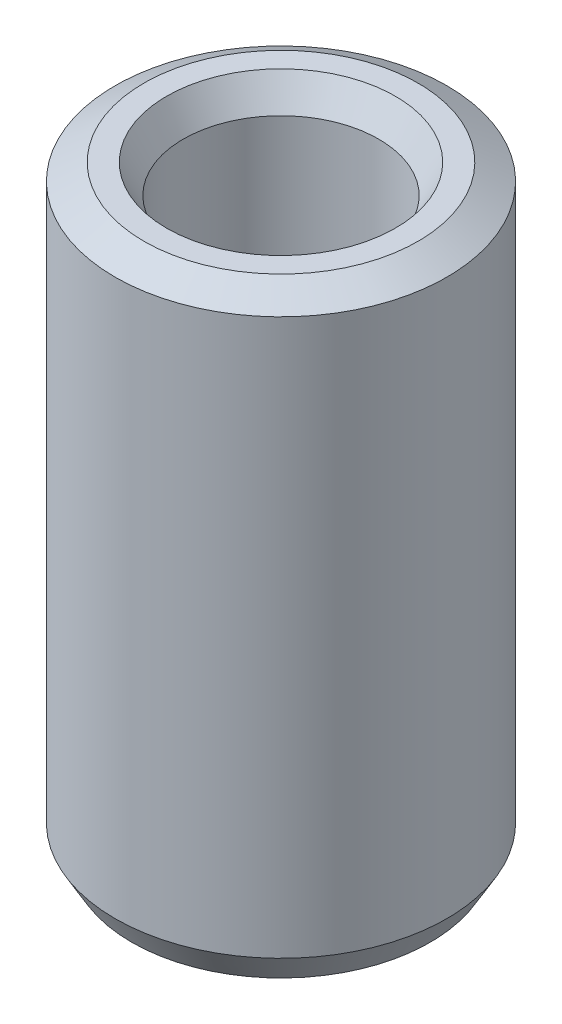
SolidWorks part; units mm, degrees
ref_plane "Front Plane" through (0, 0, 0) normal (0, 0, 1) x (1, 0, 0)
ref_plane "Top Plane" through (0, 0, 0) normal (0, 1, 0) x (1, 0, 0)
ref_plane "Right Plane" through (0, 0, 0) normal (1, 0, 0) x (0, 0, -1)
sketch "Sketch1" plane through (0, 0, 0) normal (0, 1, 0) x (1, 0, 0)
  circle A0 centre (0, 0) radius 37.5
  dimension "SLEEVE_OD" = 75
extrude "Boss-Extrude1" add sketch "Sketch1" along normal blind 135.8694
sketch "Sketch2" plane through (0, 0, 0) normal (0, 1, 0) x (1, 0, 0)
  circle A0 centre (0, 0) radius 22.0922
  dimension "BORE_D" = 44.1845
extrude "Cut-Extrude1" cut sketch "Sketch2" along normal through all
chamfer "Chamfer1" distance 3.7626 angle 60 4 edges at (0, 135.8694, 22.0922) (0, 0, 22.0922) (0, 0, 37.5) (0, 135.8694, 37.5) first distance on face at (0, 135.8694, 22.0922) first distance on face at (0, 0, 22.0922) first distance on face at (0, 135.8694, 37.5)
